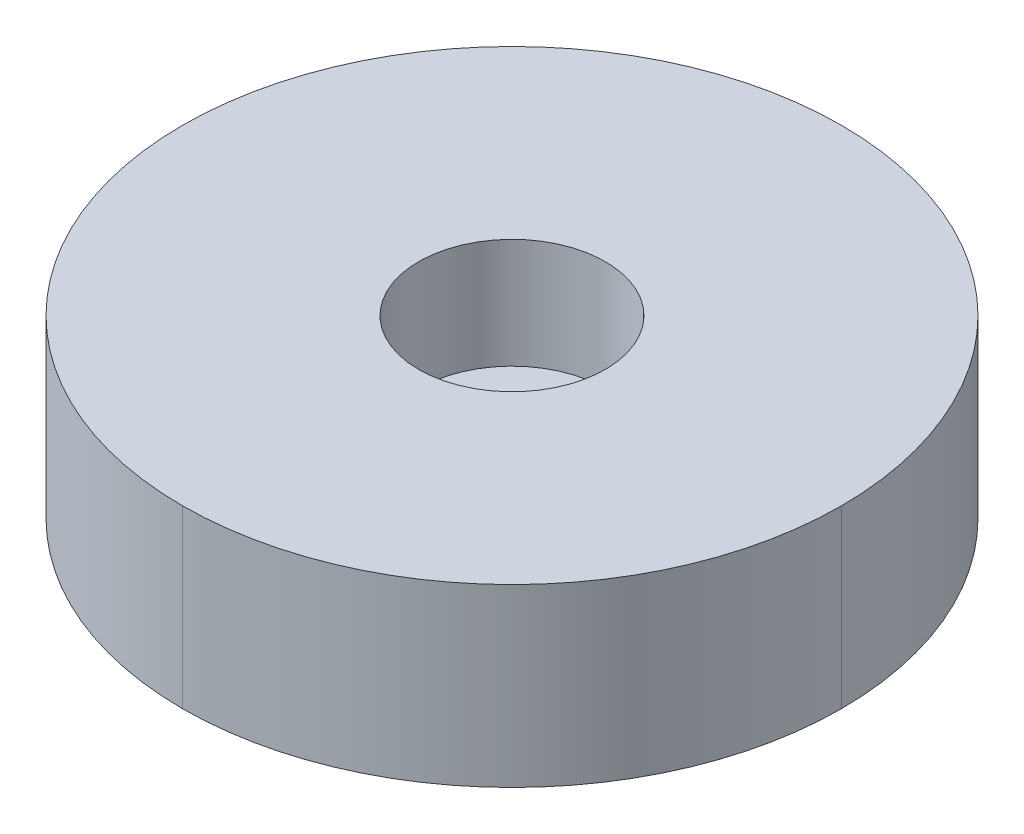
SolidWorks part; units mm, degrees
ref_plane "Front Plane" through (0, 0, 0) normal (0, 0, 1) x (1, 0, 0)
ref_plane "Top Plane" through (0, 0, 0) normal (0, 1, 0) x (1, 0, 0)
ref_plane "Right Plane" through (0, 0, 0) normal (1, 0, 0) x (0, 0, -1)
sketch "Sketch1" plane through (0, 0, 0) normal (0, 1, 0) x (1, 0, 0)
  line L1 (-19.2612, 7.058) -> (10.7388, 7.058)
  line L2 (-19.2612, 7.058) -> (-19.2612, -22.942)
  line L3 (-19.2612, -22.942) -> (10.7388, -22.942)
  line L4 (10.7388, 7.058) -> (10.7388, -22.942)
  dimension "D1" = 30
  dimension "D2" = 30
extrude "Boss-Extrude3" add sketch "Sketch1" along normal blind 8
sketch "Sketch3" plane through (0, 8, 0) normal (0, 1, 0) x (1, 0, 0)
  line L1 (-19.2612, 7.058) -> (10.7388, -22.942)
  circle A0 centre (-4.2612, -7.942) radius 4.25
  point P5 (-4.2612, -7.942)
  dimension "D1" = 8.5
extrude "Cut-Extrude2" cut sketch "Sketch3" against normal blind 5 contours A0
fillet "Fillet2" radius 15 4 edges at (10.7388, 4, 22.942) (-19.2612, 4, 22.942) (-19.2612, 4, -7.058) (10.7388, 4, -7.058)
